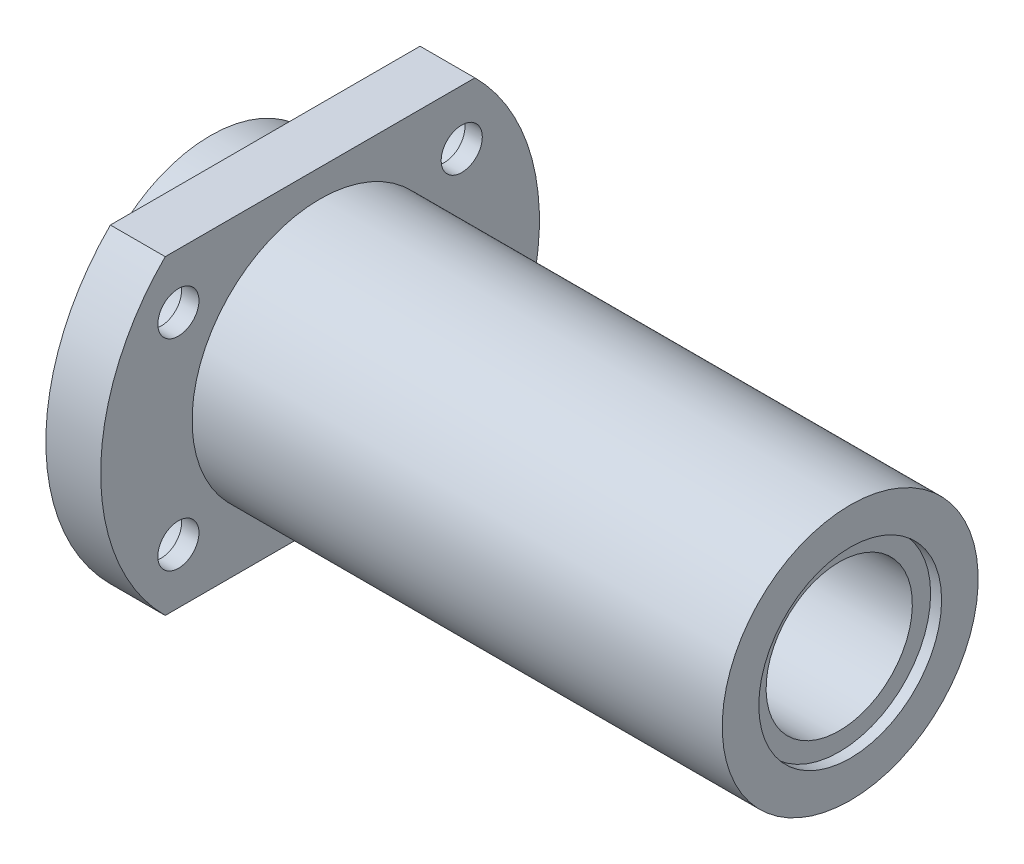
SolidWorks part; units mm, degrees
ref_plane "前视基准面" through (0, 0, 0) normal (0, 0, 1) x (1, 0, 0)
ref_plane "上视基准面" through (0, 0, 0) normal (0, 1, 0) x (1, 0, 0)
ref_plane "右视基准面" through (0, 0, 0) normal (1, 0, 0) x (0, 0, -1)
sketch "草图1" plane through (0, 0, 0) normal (0, 0, 1) x (1, 0, 0)
  line L1 (6, 24) -> (12, 24)
  line L2 (12, 24) -> (12, 14)
  line L3 (12, 14) -> (70, 14)
  line L4 (70, 14) -> (70, 0)
  line L5 (70, 0) -> (0, 0)
  line L6 (0, 10) -> (1.2, 10)
  line L7 (1.2, 10) -> (1.2, 8)
  line L8 (1.2, 8) -> (68.8, 8)
  line L9 (68.8, 8) -> (68.8, 10)
  line L10 (68.8, 10) -> (70, 10)
  line L11 (6, 0) -> (84.6332, 0) construction
  line L12 (0, 0) -> (50000, 0) construction
  line L13 (0, 0) -> (0, 50000) construction
  line L14 (6, 14) -> (0, 14)
  line L15 (0, 14) -> (0, 0)
  line L16 (6, 14) -> (6, 24)
  dimension "D4" = 20
  dimension "Df" = 48
  dimension "DD" = 28
  dimension "dr" = 16
  dimension "D5" = 1.2
  dimension "L" = 70
  dimension "t" = 6
  dimension "I" = 6
revolve "旋转1" add sketch "草图1" angle 360 about L5 region at (31.7172, 12.0303, 0)
sketch "草图4" plane through (6, 0, 0) normal (-1, 0, 0) x (0, 0, 1)
  line L0 (-25.7479, 0) -> (26.9915, 0) construction
  line L1 (0, -27.2054) -> (0, 29.7319) construction
  circle A0 centre (15.5, 11) radius 2.25
  circle A1 centre (-15.5, -11) radius 2.25
  circle A2 centre (-15.5, 11) radius 2.25
  circle A3 centre (15.5, -11) radius 2.25
  dimension "X" = 4.5
  dimension "A" = 31
  dimension "F" = 22
extrude "切除-拉伸1" cut sketch "草图4" against normal through all
sketch "草图5" plane through (6, 0, 0) normal (-1, 0, 0) x (0, 0, 1)
  circle A0 centre (15.5, 11) radius 3.75
  circle A2 centre (-15.5, 11) radius 3.75
  circle A4 centre (-15.5, -11) radius 3.75
  circle A5 centre (15.5, -11) radius 3.75
  circle A6 centre (-15.5, 11) radius 2.25 construction
  circle A7 centre (15.5, 11) radius 2.25 construction
  dimension "Y" = 7.5
extrude "切除-拉伸4" cut sketch "草图5" against normal blind 4.1
ref_axis "基准轴1" through (12, 0, 0) along (1, 0, 0)
sketch "草图7" plane through (6, 0, 0) normal (-1, 0, 0) x (0, 0, 1)
  line L0 (-16.9411, 17) -> (16.9411, 17)
  line L1 (-65.4766, 0) -> (26.0236, 0) construction
  line L2 (-16.9411, -17) -> (16.9411, -17)
  circle A1 centre (0, 0) radius 24 construction
  arc A3 (-16.9411, -17) -> (16.9411, -17) centre (0, 0) ccw
  arc A5 (16.9411, 17) -> (-16.9411, 17) centre (0, 0) ccw
  dimension "W" = 34
extrude "切除-拉伸3" cut sketch "草图7" against normal through all contours L2 | L0 region at (6, 19.8382, 0) region at (6, -19.8382, 0)
equation "\"D4@草图1\" = \"dr@草图1\"+4"
equation "\"D5@草图1\" = \"t@草图1\" / 5"
